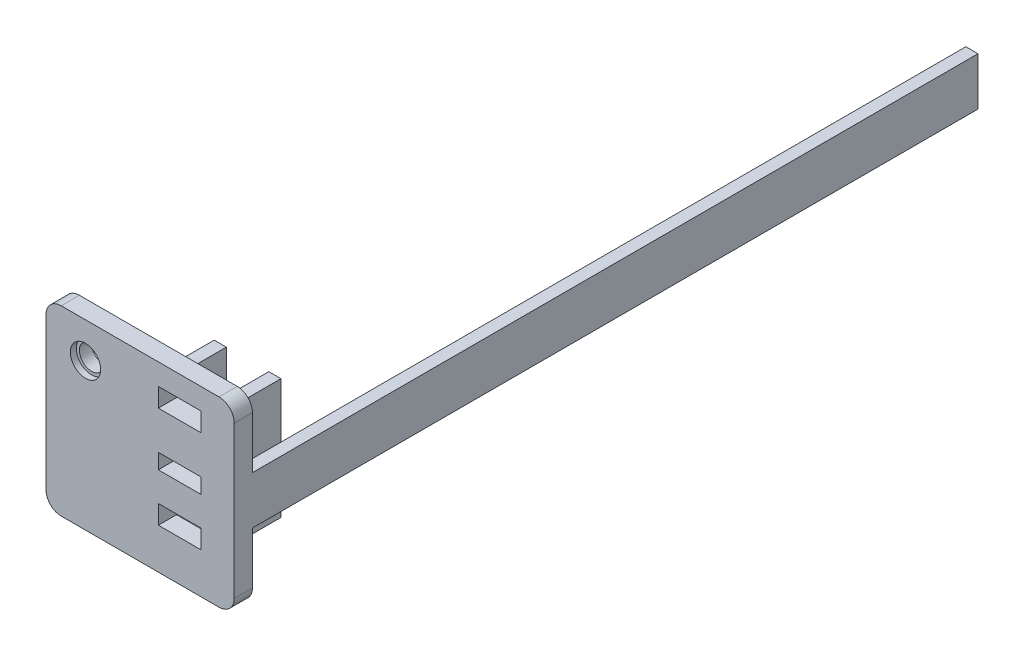
SolidWorks part; units mm, degrees
ref_plane "Alzado" through (0, 0, 0) normal (1, 0, 0) x (0, 1, 0)
ref_plane "Planta" through (0, 0, 0) normal (0, 0, 1) x (0, 1, 0)
ref_plane "Vista lateral" through (0, 0, 0) normal (0, 1, 0) x (-1, 0, 0)
sketch "Croquis2" plane through (0, 0, 0) normal (0, 0, 1) x (0, 1, 0)
  line L0 (9.15, 9) -> (9.7852, 9) construction
  line L1 (-15, -15.5) -> (15, -15.5)
  line L2 (-15, -15.5) -> (-15, 15.5)
  line L3 (-15, 15.5) -> (15, 15.5)
  line L4 (15, -15.5) -> (15, 15.5)
  line L5 (-15, -15.5) -> (15, 15.5) construction
  line L6 (-15, 15.5) -> (15, -15.5) construction
  line L7 (3.95, -15.5) -> (-3.95, -15.5)
  line L8 (3.95, -15.5) -> (3.95, -13.5)
  line L9 (3.95, -13.5) -> (-3.95, -13.5)
  line L10 (-3.95, -15.5) -> (-3.95, -13.5)
  line L11 (-10.85, 13.2) -> (3.3, 13.2)
  line L12 (-10.85, 13.2) -> (-10.85, 2.5)
  line L13 (-10.85, 2.5) -> (3.3, 2.5)
  line L14 (3.3, 13.2) -> (3.3, 2.5)
  line L15 (-13, 0.5) -> (13, 0.5) construction
  line L16 (-13, 0.5) -> (-13, -13.5) construction
  line L17 (-13, -13.5) -> (13, -13.5) construction
  line L18 (13, 0.5) -> (13, -13.5) construction
  line L19 (-8.3, -3) -> (-5.2, -3)
  line L20 (-8.3, -3) -> (-8.3, -10)
  line L21 (-8.3, -10) -> (-5.2, -10)
  line L22 (11.5, -3) -> (11.5, -10)
  line L23 (9.15, 9) -> (9.15, 8.0512) construction
  line L24 (-0.4, -3) -> (2.1, -3)
  line L25 (8.4, -3) -> (8.4, -10)
  line L26 (2.1, -10) -> (2.1, -3)
  line L27 (-0.4, -3) -> (-0.4, -10)
  line L28 (-5.2, -10) -> (-5.2, -3)
  line L29 (-0.4, -10) -> (2.1, -10)
  line L30 (8.4, -10) -> (11.5, -10)
  line L31 (8.4, -3) -> (11.5, -3)
  line L32 (8.4, -3) -> (2.1, -3)
  line L33 (2.1, -10) -> (8.4, -10)
  line L34 (-0.4, -3) -> (-5.2, -3)
  line L35 (-5.2, -10) -> (-0.4, -10)
  line L36 (11.5, -6.5) -> (10.1246, -6.5) construction
  line L37 (11.5, -3) -> (-8.3, -3)
  line L38 (11.5, -3) -> (11.5, -1)
  line L39 (11.5, -1) -> (-8.3, -1)
  line L40 (-8.3, -3) -> (-8.3, -1)
  line L41 (11.5, -12) -> (-8.3, -12)
  line L42 (-8.3, -10) -> (-8.3, -12)
  line L43 (11.5, -10) -> (-8.3, -10)
  line L44 (11.5, -10) -> (11.5, -12)
  circle A0 centre (9.15, 9) radius 2.5
  circle A1 centre (9.15, 9) radius 2
  point P0 (0, 0)
  point P10 (0, -15.5)
  point P23 (13, -6.5)
  point P24 (11.5, -6.5)
  dimension "D16" = 5
  dimension "D17" = 4
  dimension "D1" = 31
  dimension "D2" = 30
  dimension "D3" = 7.9
  dimension "D4" = 2
  dimension "D5" = 14.15
  dimension "D6" = 4.15
  dimension "D7" = 2.3
  dimension "D8" = 10.7
  dimension "D9" = 26
  dimension "D10" = 14
  dimension "D11" = 2
  dimension "D12" = 2
  dimension "D13" = 19.8
  dimension "D14" = 7
  dimension "D15" = 1.5
  dimension "D18" = 3.1
  dimension "D19" = 6.3
  dimension "D20" = 4.8
  dimension "D21" = 3.1
  dimension "D22" = 2
extrude "Saliente-Extruir1" add sketch "Croquis2" along normal blind 3 contours L10 L1 L8 L9 | L1 L10 L9 L8 L4 L3 L2 A0 L11 L14 L13 L12 L19 L22 L21 L20 | A0 A1 | L14 L11 L12 L13 | L26 L33 L25 L32 | L28 L35 L27 L34 | L40 L19 L34 L24 L32 L31 L38 L39 | L44 L30 L33 L29 L35 L21 L42 L41 region at (-0.5321, 0.0826, 0) region at (14.5, 0, 0) region at (-7.85, -3.775, 0) region at (2, 1.6, 0) region at (6.5, -2.8, 0) region at (11, 1.6, 0) region at (6.5, 5.25, 0) region at (-9, 6.7207, 0)
extrude "Cortar-Extruir1" cut sketch "Croquis2<4>" against normal blind 1 from surface contours A0 A1 region at (-9, 6.7207, 0) starting at face at (6.5, 0.85, 3)
sketch "Croquis2<4>" plane through (0, 0, 0) normal (0, 0, 1) x (0, 1, 0) same geometry as "Croquis2"
extrude "Saliente-Extruir2" add sketch "Croquis2<5>" against normal blind 2 contours L14 L11 L12 L13 region at (-7.85, -3.775, 0)
sketch "Croquis2<5>" plane through (0, 0, 0) normal (0, 0, 1) x (0, 1, 0) same geometry as "Croquis2"
extrude "Saliente-Extruir3" add sketch "Croquis2<7>" against normal blind 119.5 contours L10 L1 L8 L9 region at (14.5, 0, 0)
sketch "Croquis2<7>" plane through (0, 0, 0) normal (0, 0, 1) x (0, 1, 0) same geometry as "Croquis2"
extrude "Saliente-Extruir4" add sketch "Croquis2<9>" against normal blind 0.6 contours L28 L35 L27 L34 | L26 L33 L25 L32 region at (6.5, -2.8, 0) region at (6.5, 5.25, 0)
sketch "Croquis2<9>" plane through (0, 0, 0) normal (0, 0, 1) x (0, 1, 0) same geometry as "Croquis2"
extrude "Saliente-Extruir5" add sketch "Croquis2<11>" against normal blind 8.2 contours L40 L19 L34 L24 L32 L31 L38 L39 | L44 L30 L33 L29 L35 L21 L42 L41 region at (2, 1.6, 0) region at (11, 1.6, 0)
sketch "Croquis2<11>" plane through (0, 0, 0) normal (0, 0, 1) x (0, 1, 0) same geometry as "Croquis2"
sketch "Croquis3" plane through (3, 0, 0) normal (1, 0, 0) x (0, 1, 0)
  line L0 (8.4, -0.6) -> (2.1, -0.6) construction
  line L1 (8.4, -0.6) -> (2.1, -0.6) construction
  line L2 (6.77, -2.63) -> (6.03, -2.63)
  line L3 (6.77, -4.38) -> (6.03, -4.38)
  line L4 (11.5, -8.2) -> (11.5, 0) construction
  line L6 (-8.3, -8.2) -> (-8.3, 0) construction
  arc A0 (6.03, -2.63) -> (6.03, -4.38) centre (6.4, -3.505) ccw
  circle A1 centre (-3.1, -3.505) radius 0.95
  arc A2 (6.77, -4.38) -> (6.77, -2.63) centre (6.4, -3.505) ccw
  point P3 (7.35, -3.505)
  point P13 (-4.05, -3.505)
  dimension "D1" = 1.75
  dimension "D2" = 1.9
  dimension "D3" = 2.03
  dimension "D4" = 4.15
  dimension "D5" = 4.25
extrude "Saliente-Extruir6" add sketch "Croquis3" along normal blind 0.4
fillet "Redondeo1" radius 0.25 5 edges at (3.4, -2.15, -3.505) (3.4, 6.4, -4.38) (3.4, 5.45, -3.505) (3.4, 6.4, -2.63) (3.4, 7.35, -3.505)
ref_plane "Plano1" through (6.5, 0, 0) normal (1, 0, 0) x (0, 0, -1)
mirror "Simetría1" about plane through (6.5, 0, 0) normal (1, 0, 0) of "Redondeo1", "Saliente-Extruir6"
fillet "Redondeo2" radius 2.5 4 edges at (15.5, 15, 1.5) (15.5, -15, 1.5) (-15.5, -15, 1.5) (-15.5, 15, 1.5)
